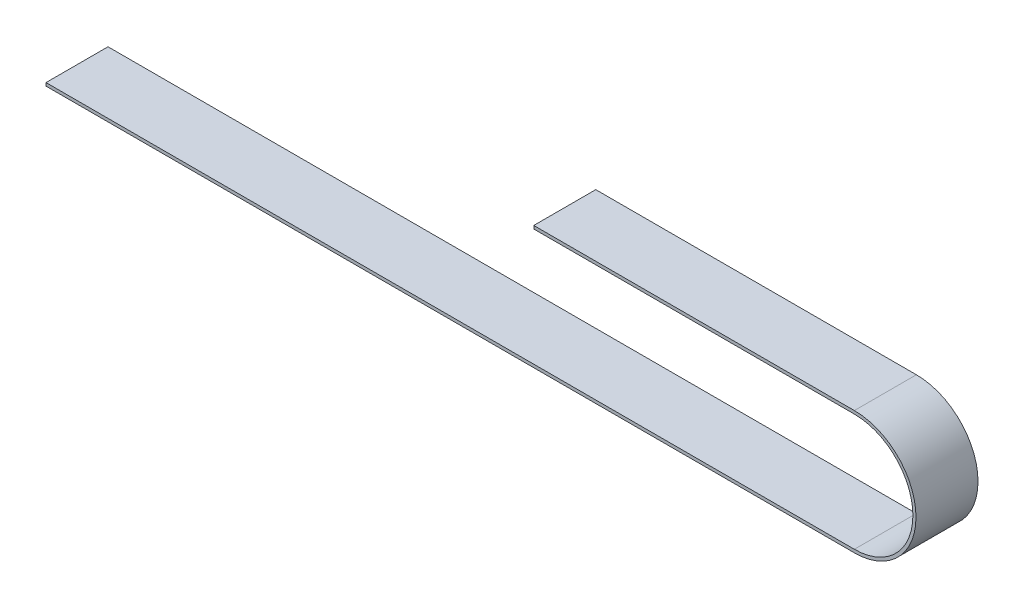
SolidWorks part; units mm, degrees
ref_plane "Front Plane" through (0, 0, 0) normal (0, 0, 1) x (1, 0, 0)
ref_plane "Top Plane" through (0, 0, 0) normal (0, 1, 0) x (1, 0, 0)
ref_plane "Right Plane" through (0, 0, 0) normal (1, 0, 0) x (0, 0, -1)
sketch "Sketch1" plane through (0, 0, 0) normal (0, 0, 1) x (1, 0, 0)
  line L0 (0, 55) -> (521.4472, 55)
  line L1 (0, 60) -> (0, 50) construction
  line L2 (521.4472, 132.5) -> (314.6312, 132.5)
  line L3 (314.6312, 127.5) -> (314.6312, 137.5) construction
  arc A0 (521.4472, 55) -> (521.4472, 132.5) centre (521.4472, 93.75) ccw
  dimension "D1" = 850
extrude "Extrude-Thin1" add sketch "Sketch1" against normal blind 40 from offset 5 thin contours L0 A0 L2 offset against normal yes thin type mid plane wall 2
